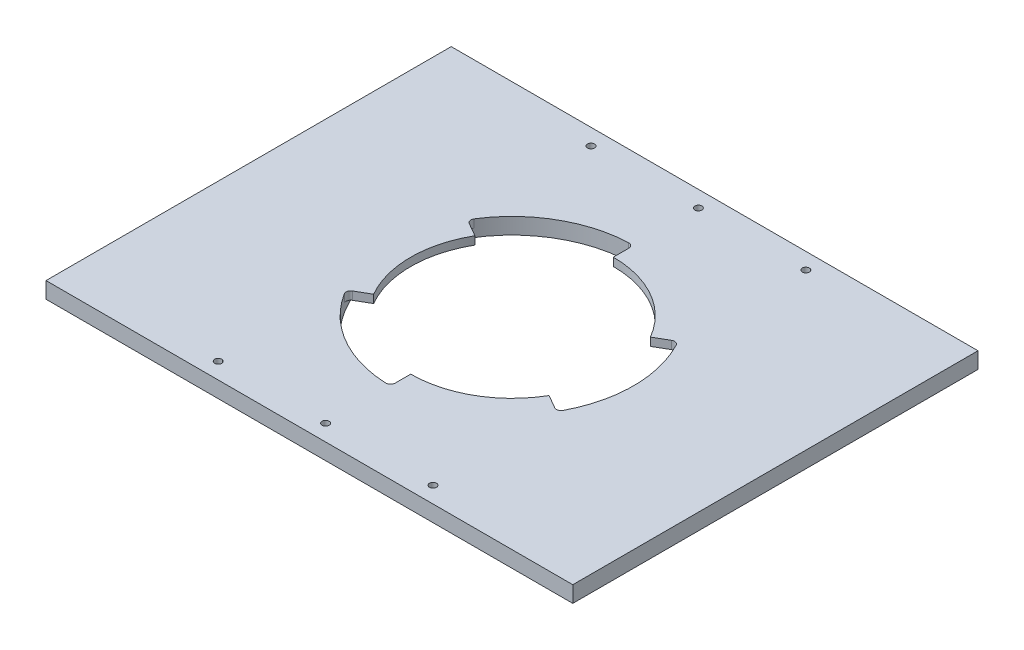
SolidWorks part; units mm, degrees
ref_plane "Ebene vorne" through (0, 0, 0) normal (0, 0, 1) x (1, 0, 0)
ref_plane "Ebene oben" through (0, 0, 0) normal (0, 1, 0) x (1, 0, 0)
ref_plane "Ebene rechts" through (0, 0, 0) normal (1, 0, 0) x (0, 0, -1)
sketch "Skizze1" plane through (0, 0, 0) normal (0, 1, 0) x (1, 0, 0)
  line L0 (-53, -92) -> (53, -92) construction
  line L1 (-130, -100) -> (130, -100)
  line L2 (-130, -100) -> (-130, 100)
  line L3 (-130, 100) -> (130, 100)
  line L4 (130, -100) -> (130, 100)
  line L5 (-130, -100) -> (130, 100) construction
  line L6 (-130, 100) -> (130, -100) construction
  line L7 (0, -100) -> (0, 100) construction
  line L8 (-130, 0) -> (130, 0) construction
  line L9 (-53, 92) -> (53, 92) construction
  circle A0 centre (-53, -92) radius 1.75
  circle A1 centre (53, -92) radius 1.75
  circle A2 centre (0, -92) radius 1.75
  circle A3 centre (0, 92) radius 1.75
  circle A4 centre (53, 92) radius 1.75
  circle A5 centre (-53, 92) radius 1.75
  point P0 (0, 0)
  point P15 (0, 0)
  point P18 (0, 0)
  dimension "D3" = 3.5
  dimension "D4" = 3.5
  dimension "D7" = 3.5
  dimension "D1" = 200
  dimension "D2" = 260
  dimension "D5" = 106
  dimension "D6" = 8
extrude "Aufsatz-Linear austragen1" add sketch "Skizze1" along normal blind 8
sketch "Skizze2" plane through (0, 8, 0) normal (0, 1, 0) x (1, 0, 0)
  circle A0 centre (0, 0) radius 50
  dimension "D1" = 100
extrude "Schnitt-Linear austragen1" cut sketch "Skizze2" against normal up to surface (8 mm away) up to face at (53, 0, -93.75)
sketch "Skizze3" plane through (0, 0, 0) normal (0, -1, 0) x (1, 0, 0)
  line L0 (-51.9615, 30) -> (-43.3013, 25)
  line L1 (-43.3013, 25) -> (0, 0) construction
  line L2 (0, 0) -> (0, 50) construction
  line L3 (0, 50) -> (0, 60)
  line L4 (51.9615, 30) -> (43.3013, 25)
  line L5 (43.3013, -25) -> (51.9615, -30)
  line L6 (0, -60) -> (0, -50)
  line L7 (-43.3013, -25) -> (-51.9615, -30)
  line L8 (0, 0) -> (60, 0) construction
  line L9 (0, 0) -> (-60, 0) construction
  line L10 (70.2506, 5) -> (49.7494, -5) construction
  line L11 (-70.2506, -5) -> (-49.7494, -5)
  line L12 (-70.2506, -5) -> (-70.2506, 5)
  line L13 (-70.2506, 5) -> (-49.7494, 5)
  line L14 (-49.7494, -5) -> (-49.7494, 5)
  line L15 (-70.2506, -5) -> (-49.7494, 5) construction
  line L16 (-70.2506, 5) -> (-49.7494, -5) construction
  line L17 (70.2506, -5) -> (49.7494, 5) construction
  line L18 (49.7494, -5) -> (49.7494, 5)
  line L19 (70.2506, 5) -> (49.7494, 5)
  line L20 (70.2506, -5) -> (70.2506, 5)
  line L21 (70.2506, -5) -> (49.7494, -5)
  circle A0 centre (0, 0) radius 60
  circle A1 centre (0, 0) radius 50 construction
  circle A2 centre (0, 0) radius 50
  point P19 (0, 0)
  point P22 (0, 0)
  circle M10 centre (0, 0) radius 50
  dimension "D1" = 10
  dimension "D2" = 60
  dimension "D4" = 10
  dimension "D3" = 3
extrude "Schnitt-Linear austragen4" cut sketch "Skizze3" against normal through all contours L21 A0 L19 M10 | L19 A0 L4 M10 | L5 A0 L21 M10 | L7 A0 L6 M10 | L3 A0 L0 M10 region at (-26.3329, 0, 45.6099) region at (52.1907, 0, 16.5552) region at (54.9234, 0, 0) region at (-26.3329, 0, -45.6099) region at (52.1907, 0, -16.5552)
extrude "Schnitt-Linear austragen5" cut sketch "Skizze3<5>" against normal blind 4 contours A0 L21 L20 L19 | A0 L13 L12 L11 | L11 A0 L7 M10 | L13 A0 L11 M10 | L0 A0 L13 M10 | L4 A0 L3 M10 | L6 A0 L5 M10 region at (-52.1907, 0, 16.5552) region at (26.3329, 0, 45.6099) region at (-65.0904, 0, 0) region at (-54.9234, 0, 0) region at (-52.1907, 0, -16.5552) region at (65.0904, 0, 0) region at (26.3329, 0, -45.6099)
sketch "Skizze3<5>" plane through (0, 0, 0) normal (0, -1, 0) x (1, 0, 0) same geometry as "Skizze3"
fillet "Verrundung1" radius 2.3 10 edges at (70.2506, 2, -5) (70.2506, 2, 5) (-70.2506, 2, -5) (-70.2506, 2, 5) (51.9615, 6, -30) (0, 6, -60) (-51.9615, 6, -30) (-51.9615, 6, 30) (0, 6, 60) (51.9615, 6, 30)
